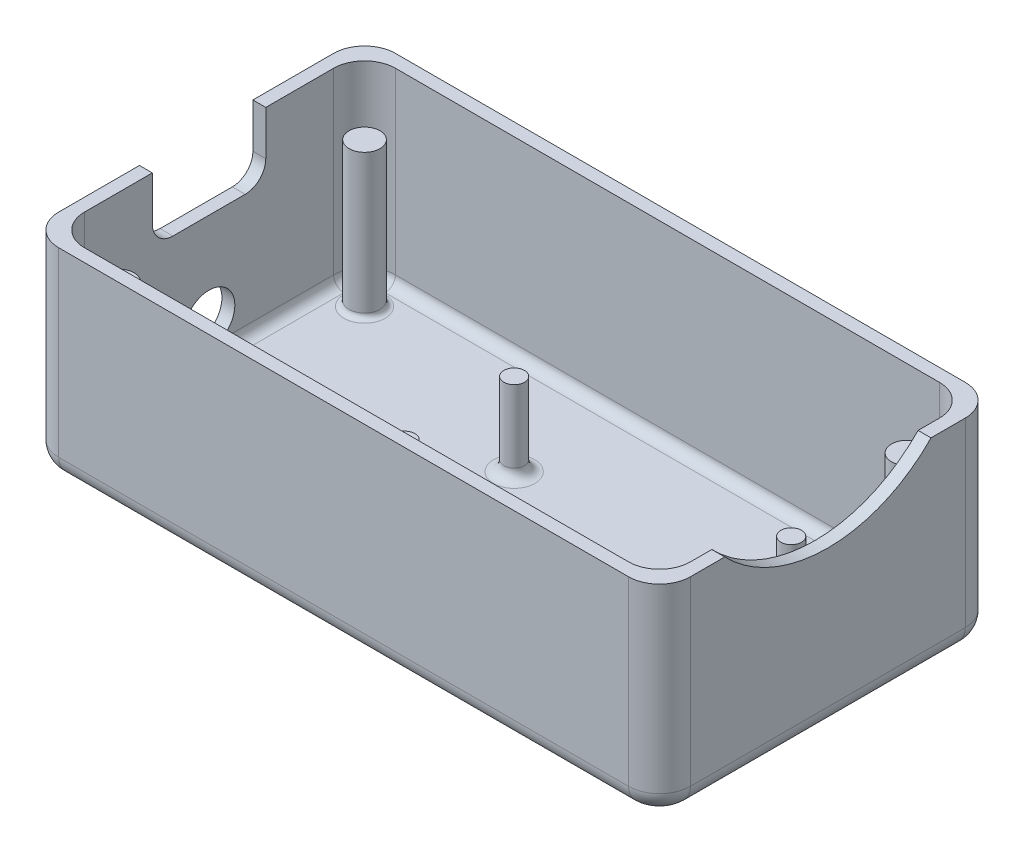
SolidWorks part; units mm, degrees
ref_plane "Front Plane" through (0, 0, 0) normal (0, 0, 1) x (1, 0, 0)
ref_plane "Top Plane" through (0, 0, 0) normal (0, 1, 0) x (1, 0, 0)
ref_plane "Right Plane" through (0, 0, 0) normal (1, 0, 0) x (0, 0, -1)
sketch "Sketch2" plane through (0, 0, 0) normal (0, 1, 0) x (1, 0, 0)
  line L0 (-52.9, -30.15) -> (-0.15, -30.15)
  line L1 (-55.9, -27.15) -> (-55.9, -3)
  line L2 (-52.9, 0) -> (-0.15, 0)
  line L3 (2.85, -27.15) -> (2.85, -3)
  line L4 (-54.15, 1.25) -> (1.1, 1.25)
  line L5 (-57.15, -1.75) -> (-57.15, -28.4)
  line L6 (-54.15, -31.4) -> (1.1, -31.4)
  line L7 (4.1, -1.75) -> (4.1, -28.4)
  line L12 (2.85, 0) -> (-55.9, 0) construction
  line L13 (-55.9, 0) -> (-55.9, -30.15) construction
  line L14 (-55.9, -30.15) -> (2.85, -30.15) construction
  line L15 (2.85, -30.15) -> (2.85, 0) construction
  arc A0 (-52.9, -30.15) -> (-55.9, -27.15) centre (-52.9, -27.15) cw
  arc A1 (-0.15, -30.15) -> (2.85, -27.15) centre (-0.15, -27.15) ccw
  arc A2 (-0.15, 0) -> (2.85, -3) centre (-0.15, -3) cw
  arc A3 (-55.9, -3) -> (-52.9, 0) centre (-52.9, -3) cw
  arc A4 (-57.15, -28.4) -> (-54.15, -31.4) centre (-54.15, -28.4) ccw
  arc A5 (1.1, -31.4) -> (4.1, -28.4) centre (1.1, -28.4) ccw
  arc A6 (1.1, 1.25) -> (4.1, -1.75) centre (1.1, -1.75) cw
  arc A7 (-54.15, 1.25) -> (-57.15, -1.75) centre (-54.15, -1.75) ccw
  dimension "D5" = 3
  dimension "D6" = 3
  dimension "D1" = 1.25
  dimension "D2" = 1.25
  dimension "D3" = 1.25
  dimension "D4" = 1.25
  dimension "D7" = 58.75
  dimension "D8" = 30.15
extrude "Boss-Extrude2" add sketch "Sketch2" along normal blind 19.6
sketch "Sketch3" plane through (0, 0, 0) normal (0, 1, 0) x (1, 0, 0)
  line L0 (-55.9, 0) -> (-55.9, -30.15)
  line L1 (-55.9, -30.15) -> (2.85, -30.15)
  line L2 (2.85, -30.15) -> (2.85, 0)
  line L3 (2.85, 0) -> (-55.9, 0)
  line L6 (2.85, -27.15) -> (2.85, -3) construction
  line L7 (-0.15, 0) -> (-52.9, 0) construction
  line L8 (-52.9, -30.15) -> (-0.15, -30.15) construction
  line L9 (-55.9, -3) -> (-55.9, -27.15) construction
extrude "Boss-Extrude3" add sketch "Sketch3" along normal blind 1.25
sketch "Sketch5" plane through (0, 1.25, 0) normal (0, 1, 0) x (1, 0, 0)
  line L0 (-26.525, 0) -> (-26.525, -30.15) construction
  line L1 (-0.15, 0) -> (-52.9, 0) construction
  line L2 (-52.9, -30.15) -> (-0.15, -30.15) construction
  line L3 (-55.9, -15.075) -> (2.85, -15.075) construction
  line L4 (-55.9, -3) -> (-55.9, -27.15) construction
  line L5 (2.85, -27.15) -> (2.85, -3) construction
  line L7 (-0.15, -30) -> (-52.75, -30)
  line L8 (2.85, -27) -> (2.85, -3.15)
  line L10 (-55.75, -27) -> (-55.75, -3.15)
  line L11 (2.85, -30) -> (-56.1889, -0.0032) construction
  line L12 (2.8174, -0.0901) -> (-55.75, -30) construction
  arc A0 (-0.15, -30) -> (2.85, -27) centre (-0.15, -27) ccw
  arc A1 (2.85, -3.15) -> (-0.15, -0.15) centre (-0.15, -3.15) ccw
  arc A2 (-52.75, -0.15) -> (-55.75, -3.15) centre (-52.75, -3.15) ccw
  arc A3 (-52.75, -30) -> (-55.75, -27) centre (-52.75, -27) cw
  circle A4 centre (-52.75, -3.15) radius 1.5
  circle A5 centre (-0.15, -3.15) radius 1.5
  circle A6 centre (-0.15, -27) radius 1.5
  circle A7 centre (-52.75, -27) radius 1.5
  point P12 (-26.525, -15.075)
  dimension "D3" = 3
  dimension "D4" = 3
  dimension "D1" = 30
  dimension "D2" = 58.6
  dimension "D5" = 2
extrude "Boss-Extrude4" add sketch "Sketch5" along normal blind 14 contours A4 | A5 | A6 | A7 region at (-52.75, 1.25, 3.15) region at (-0.15, 1.25, 3.15) region at (-0.15, 1.25, 27) region at (-52.75, 1.25, 27)
fillet "Fillet1" radius 0.5 4 edges at (-0.15, 1.25, 28.5) (-52.75, 1.25, 28.5) (-0.15, 1.25, 4.65) (-52.75, 1.25, 4.65)
sketch "Sketch6" plane through (0, 1.25, 0) normal (0, 1, 0) x (1, 0, 0)
  line L0 (-26.525, 0) -> (-26.525, -30.15) construction
  line L1 (-0.15, 0) -> (-52.9, 0) construction
  line L2 (-52.9, -30.15) -> (-0.15, -30.15) construction
  line L3 (-55.9, -15.075) -> (2.85, -15.075) construction
  line L4 (-55.9, -3) -> (-55.9, -27.15) construction
  line L5 (2.85, -27.15) -> (2.85, -3) construction
  line L6 (-2.225, -0.075) -> (-2.225, -30.075) construction
  line L7 (-55.825, -30.075) -> (2.775, -30.075)
  line L8 (-55.825, -30.075) -> (-55.825, -0.075)
  line L9 (-55.825, -0.075) -> (2.775, -0.075)
  line L10 (2.775, -30.075) -> (2.775, -0.075)
  line L11 (-55.825, -30.075) -> (2.775, -0.075) construction
  line L12 (-55.825, -0.075) -> (2.775, -30.075) construction
  line L13 (-2.225, -22.925) -> (-2.225, -7.225)
  line L14 (-2.225, -22.925) -> (-12.15, -22.925)
  line L16 (-12.225, -7.225) -> (-2.225, -7.225)
  line L17 (-2.225, -15.075) -> (-31.625, -15.075)
  circle A0 centre (-4.765, -20.385) radius 1
  circle A1 centre (-4.765, -9.765) radius 1
  circle A2 centre (-31.625, -20.385) radius 1
  circle A3 centre (-31.625, -9.765) radius 1
  point P12 (-26.525, -15.075)
  point P24 (-2.225, -15.075)
  dimension "D6" = 2
  dimension "D1" = 58.6
  dimension "D2" = 30
  dimension "D3" = 5
  dimension "D4" = 15.7
  dimension "D5" = 10
  dimension "D7" = 2.54
  dimension "D8" = 2.54
  dimension "D9" = 29.4
  dimension "D10" = 2
extrude "Boss-Extrude6" add sketch "Sketch6" along normal blind 8 contours A2 | A3 | A1 | A0 region at (-4.765, 1.25, 20.385) region at (-4.765, 1.25, 9.765) region at (-31.625, 1.25, 20.385) region at (-31.625, 1.25, 9.765)
fillet "Fillet3" radius 1 4 edges at (-4.765, 1.25, 21.385) (-4.765, 1.25, 10.765) (-31.625, 1.25, 10.765) (-31.625, 1.25, 21.385)
fillet "Fillet4" radius 2 8 edges at (-26.525, 0, 31.4) (3.2213, 0, 30.5213) (4.1, 0, 15.075) (3.2213, 0, -0.3713) (-26.525, 0, -1.25) (-56.2713, 0, -0.3713) (-57.15, 0, 15.075) (-56.2713, 0, 30.5213)
sketch "Sketch7" plane through (-57.15, 0, 0) normal (-1, 0, 0) x (0, 0, 1)
  line L1 (1.75, 19.6) -> (28.4, 19.6) construction
  line L6 (9.575, 19.6) -> (9.575, 13.3)
  line L7 (9.575, 13.3) -> (20.575, 13.3)
  line L8 (20.575, 13.3) -> (20.575, 19.6)
  line L9 (15.075, 19.6) -> (15.075, 2) construction
  line L10 (1.75, 2) -> (28.4, 2) construction
  line L11 (9.575, 19.6) -> (20.575, 19.6)
  circle A0 centre (15.075, 4.5) radius 2.5
  point P11 (15.075, 13.3)
  dimension "D3" = 5
  dimension "D1" = 11
  dimension "D2" = 6.3
extrude "Cut-Extrude1" cut sketch "Sketch7" against normal blind 2
fillet "Fillet7" radius 1 8 edges at (-55.9, 1.25, 15.075) (-26.525, 1.25, 30.15) (2.85, 1.25, 15.075) (-26.525, 1.25, 0) (1.9713, 1.25, 0.8787) (1.9713, 1.25, 29.2713) (-55.0213, 1.25, 29.2713) (-55.0213, 1.25, 0.8787)
sketch "Sketch8" plane through (4.1, 0, 0) normal (1, 0, 0) x (0, 0, -1)
  line L0 (-28.4, 19.6) -> (-1.75, 19.6) construction
  line L1 (-15.075, 19.6) -> (-15.075, 2) construction
  line L2 (-28.4, 2) -> (-1.75, 2) construction
  line L3 (-30.075, 19.6) -> (-0.075, 19.6)
  line L4 (-25.075, 19.6) -> (-5.075, 19.6)
  arc A0 (-25.075, 19.6) -> (-5.075, 19.6) centre (-15.075, 29.2397) ccw
  point P9 (-15.075, 15.35)
  point P15 (-15.075, 19.6)
  dimension "D1" = 4.25
  dimension "D2" = 30
  dimension "D3" = 5
extrude "Cut-Extrude2" cut sketch "Sketch8" against normal blind 2 contours L1 L4 A0 | L3 L1 A0 region at (4.1, 17.8755, 11.2346) region at (4.1, 17.8755, 18.9154)
fillet "Fillet8" radius 2 2 edges at (-56.525, 13.3, 20.575) (-56.525, 13.3, 9.575)
